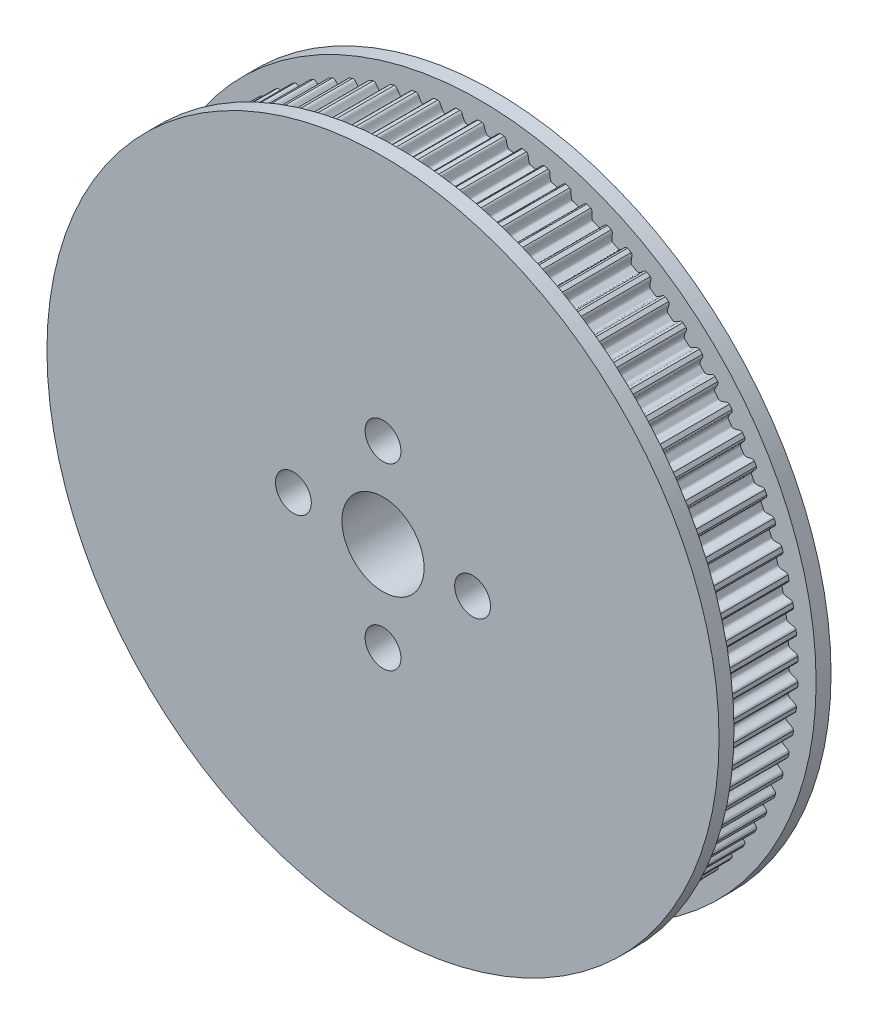
SolidWorks part; units mm, degrees
ref_plane "前视基准面" through (0, 0, 0) normal (0, 0, 1) x (1, 0, 0)
ref_plane "上视基准面" through (0, 0, 0) normal (0, 1, 0) x (1, 0, 0)
ref_plane "右视基准面" through (0, 0, 0) normal (1, 0, 0) x (0, 0, -1)
other "Configuration Table"
ref_axis "基准轴1" through (0, 0, 55) along (0, 0, -1)
sketch "SketchRevolveGearBelt01" plane through (0, 0, 0) normal (1, 0, 0) x (0, 0, -1)
  line L0 (0, 0) -> (1, 0) construction
  line L1 (9.774, 0) -> (9.774, 40.5718)
  line L2 (9.774, 40.5718) -> (9.012, 40.5718)
  line L3 (9.012, 40.5718) -> (9.012, 42.8203)
  line L4 (9.012, 42.8203) -> (9.48, 43.9502)
  line L5 (9.48, 43.9502) -> (8.7761, 44.2418)
  line L6 (8.7761, 44.2418) -> (8.25, 42.9718)
  line L7 (8.25, 42.9718) -> (8.25, 42.5769)
  line L8 (8.25, 42.5769) -> (-8.25, 42.5769)
  line L9 (-8.25, 42.5769) -> (-8.25, 42.9718)
  line L10 (-8.25, 42.9718) -> (-8.7761, 44.2418)
  line L11 (-8.7761, 44.2418) -> (-9.48, 43.9502)
  line L12 (-9.48, 43.9502) -> (-9.012, 42.8203)
  line L13 (-9.012, 42.8203) -> (-9.012, 40.5718)
  line L14 (-9.012, 40.5718) -> (-9.774, 40.5718)
  line L15 (-9.774, 40.5718) -> (-9.774, 0)
  line L16 (-9.774, 0) -> (9.774, 0)
  dimension "GearBeltFlange1OutsideLength" = 2.2484
  dimension "GearBeltFlange1X" = 0.468
  dimension "GearBeltFlange1Y" = 1.13
  dimension "GearBeltFlangeThickness" = 0.762
  dimension "GearBeltFlangeInside" = 0.395
  dimension "GearBeltOutsideDiameter" = 42.5769
  dimension "GearBeltFlange2X" = 0.468
revolve "Gates_PowerGrip_GT_3mm, 15mm Belt Width" add sketch "SketchRevolveGearBelt01" angle 360 about L0
sketch "SketchToothGearBelt01" plane through (0, 0, 0) normal (0, 0, 1) x (1, 0, 0)
  arc A0 (42.5707, 1.2903) -> (42.5707, -1.2903) centre (0, 0) cw
  spline S0 degree 3 poles (42.5707, -1.2903) (42.5702, -1.2648) (42.5657, -1.2267) (42.5525, -1.1775) (42.5392, -1.1417) (42.5225, -1.1073) (42.5026, -1.0746) (42.4797, -1.044) (42.454, -1.0157) (42.4256, -0.99) (42.395, -0.9672) (42.3623, -0.9473) (42.328, -0.9305) (42.2614, -0.907) (42.1782, -0.8819) (42.081, -0.8512) (42.0023, -0.8247) (41.9284, -0.7983) (41.8593, -0.7718) (41.7949, -0.7454) (41.7352, -0.7189) (41.6803, -0.6925) (41.6302, -0.666) (41.5848, -0.6396) (41.5442, -0.6131) (41.5083, -0.5867) (41.4771, -0.5602) (41.4507, -0.5337) (41.429, -0.5071) (41.412, -0.4805) (41.3999, -0.4538) (41.3923, -0.4269) (41.389, -0.3755) (41.3938, -0.3) (41.394, -0.2) (41.3952, -0.1) (41.3953, 0) (41.3952, 0.1) (41.394, 0.2) (41.3938, 0.3) (41.389, 0.3755) (41.3923, 0.4269) (41.3999, 0.4538) (41.412, 0.4805) (41.429, 0.5071) (41.4507, 0.5337) (41.4771, 0.5602) (41.5083, 0.5867) (41.5442, 0.6131) (41.5848, 0.6396) (41.6302, 0.666) (41.6803, 0.6925) (41.7352, 0.7189) (41.7949, 0.7454) (41.8593, 0.7718) (41.9284, 0.7983) (42.0023, 0.8247) (42.081, 0.8512) (42.1782, 0.8819) (42.2614, 0.907) (42.328, 0.9305) (42.3623, 0.9473) (42.395, 0.9672) (42.4256, 0.99) (42.454, 1.0157) (42.4797, 1.044) (42.5026, 1.0746) (42.5225, 1.1073) (42.5392, 1.1417) (42.5525, 1.1775) (42.5657, 1.2267) (42.5702, 1.2648) (42.5707, 1.2903) knots 0 0 0 0 0.019289 0.028934 0.038579 0.048223 0.057868 0.067513 0.077157 0.086802 0.096447 0.106091 0.115736 0.125381 0.159545 0.181662 0.202634 0.222468 0.241173 0.258759 0.275237 0.290622 0.304933 0.318191 0.330424 0.341669 0.351971 0.361391 0.370006 0.377918 0.38526 0.392196 0.398919 0.424208 0.449472 0.474736 0.5 0.525264 0.550528 0.575792 0.601081 0.607804 0.61474 0.622082 0.629994 0.638609 0.648029 0.658331 0.669576 0.681809 0.695067 0.709378 0.724763 0.741241 0.758827 0.777532 0.797366 0.818338 0.840455 0.874619 0.884264 0.893909 0.903553 0.913198 0.922843 0.932487 0.942132 0.951777 0.961421 0.971066 0.980711 1 1 1 1
extrude "ToothExtrudeCutGearBelt01" cut sketch "SketchToothGearBelt01" against normal blind 8.25 and the other way blind 8.25
pattern_circular "Tooth Pattern, 90" count 90 every 4 about axis through (0, 0, 55) along (0, 0, -1) of "ToothExtrudeCutGearBelt01"
sketch "BoreRevolveSketch" plane through (0, 0, 0) normal (1, 0, 0) x (0, 0, -1)
  line L0 (0, 0) -> (1, 0) construction
  line L1 (-9.774, 0) -> (9.774, 0)
  line L2 (9.774, 0) -> (9.774, 5)
  line L3 (9.774, 5) -> (-9.774, 5)
  line L4 (-9.774, 5) -> (-9.774, 0)
  dimension "TaperSide1" = 5
  dimension "TaperSide2" = 5
revolve "BoreRevolveCut" cut sketch "BoreRevolveSketch" angle 360 about L0
sketch "AuxiliarySketchGearBelt01" plane through (0, 0, 0) normal (0, 0, 1) x (1, 0, 0)
  circle A0 centre (0, 0) radius 42.9718 construction
  dimension "PitchDiameter" = 85.9437
sketch "草图5" plane through (0, 0, 9.774) normal (0, 0, 1) x (1, 0, 0)
  circle A0 centre (0, 0) radius 50.6338
extrude "切除-拉伸2" cut sketch "草图5" against normal blind 4.55
sketch "草图7" plane through (0, 0, -9.774) normal (0, 0, -1) x (-1, 0, 0)
  circle A0 centre (0, 0) radius 52.5831
extrude "切除-拉伸3" cut sketch "草图7" against normal blind 4
sketch "草图8" plane through (0, 0, 5.224) normal (0, 0, 1) x (1, 0, 0)
  circle A0 centre (0, 0) radius 45
  dimension "D1" = 90
extrude "凸台-拉伸1" add sketch "草图8" along normal blind 2
sketch "草图9" plane through (0, 0, -5.774) normal (0, 0, -1) x (-1, 0, 0)
  circle A0 centre (0, 0) radius 45
extrude "凸台-拉伸2" add sketch "草图9" along normal blind 2
sketch "草图10" plane through (0, 0, -7.774) normal (0, 0, -1) x (-1, 0, 0)
  circle A0 centre (0, 0) radius 5.5
  dimension "D1" = 11
extrude "切除-拉伸4" cut sketch "草图10" against normal blind 20
sketch "草图11" plane through (0, 0, 7.224) normal (0, 0, 1) x (1, 0, 0)
  circle A0 centre (0, 0) radius 12
  circle A1 centre (0, 12) radius 2.4
  circle A2 centre (12, 0) radius 2.4
  circle A3 centre (0, -12) radius 2.4
  circle A4 centre (-12, 0) radius 2.4
  point P14 (0, 0)
  dimension "D1" = 24
  dimension "D2" = 4.8
  dimension "D3" = 4
extrude "切除-拉伸5" cut sketch "草图11" against normal blind 20 contours A1 | A2 | A3 | A4
